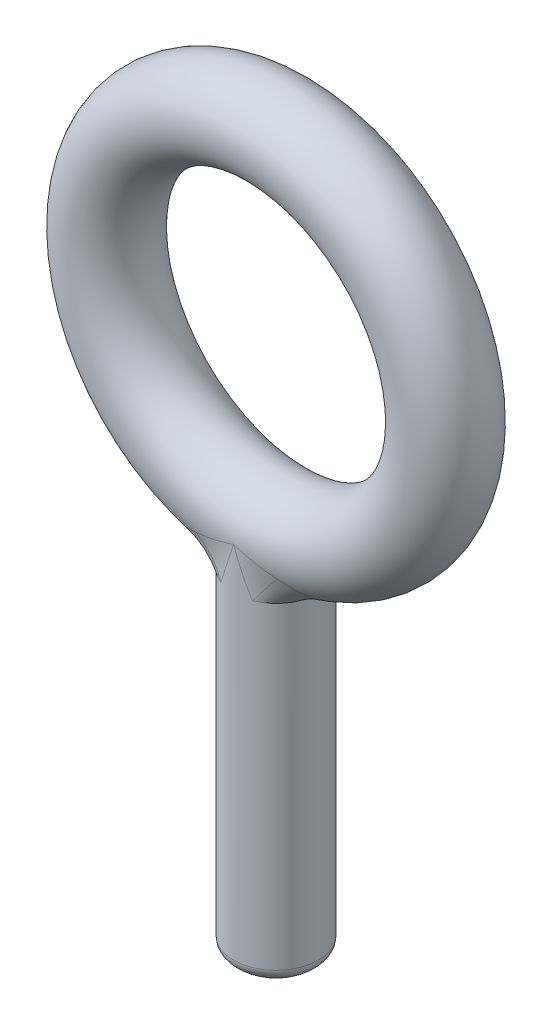
SolidWorks part; units mm, degrees
ref_plane "Front Plane" through (0, 0, 0) normal (0, 0, 1) x (1, 0, 0)
ref_plane "Top Plane" through (0, 0, 0) normal (0, 1, 0) x (1, 0, 0)
ref_plane "Right Plane" through (0, 0, 0) normal (1, 0, 0) x (0, 0, -1)
sketch "Sketch1" plane through (0, 0, 0) normal (0, 0, 1) x (1, 0, 0)
  line L0 (0, -15.875) -> (0, -41.275) construction
  line L1 (-3.175, -41.275) -> (3.175, -41.275) construction
  line L3 (0, -15.875) -> (0, -9.525) construction
  circle A0 centre (0, 0) radius 15.875 construction
  circle A1 centre (0, 12.7) radius 3.175 construction
  circle A2 centre (0, 0) radius 9.525 construction
  point P7 (0, -15.875)
  point P9 (0, -15.875)
  point P10 (0, 15.875)
  point P11 (0, 9.525)
  point P14 (0, -41.275)
  point P19 (0, -12.7)
  dimension "A" = 6.35
  dimension "Eye Dia." = 19.05
  dimension "Overall Lg." = 57.15
  dimension "Shank Lg." = 25.4
  dimension "OD" = 31.75
  dimension "Shank OD" = 6.35
sketch "Sketch2" plane through (0, 0, 0) normal (0, 1, 0) x (1, 0, 0)
  circle A0 centre (0, 0) radius 3.175
extrude "Boss-Extrude1" add sketch "Sketch2" against normal up to vertex (41.275 mm away) from vertex up to point (0, -41.275, 0) starting at point (0, -15.875, 0)
sketch "Sketch3" plane through (0, 0, 0) normal (1, 0, 0) x (0, 0, -1)
  circle A0 centre (0, 12.7) radius 3.175
ref_axis "Axis1" through (0, 0, -34.925) along (0, 0, 1)
revolve "Revolve1" add sketch "Sketch3" angle 360 about axis through (0, 0, -34.925) along (0, 0, 1)
sketch "Sketch4" plane through (0, -15.875, 0) normal (0, 1, 0) x (1, 0, 0)
  circle A1 centre (0, 0) radius 3.175
  circle A2 centre (0, 0) radius 3.175
  dimension "D1" = 0
extrude "Boss-Extrude2" [suppressed] add sketch "Sketch4" along normal up to vertex (9.525 mm away) up to point (0, -15.875, 0)
sketch "Sketch5" plane through (0, 0, 0) normal (0, 0, 1) x (1, 0, 0)
  line L0 (0, -15.875) -> (0, -12.7)
  line L1 (-3.175, -15.875) -> (0, -15.875)
  line L2 (-3.175, -12.7) -> (0, -12.7)
  line L3 (-3.175, -15.875) -> (-3.175, -12.7)
  line L4 (0, -15.875) -> (0, -9.525) construction
  circle A0 centre (0, -12.7) radius 3.175 construction
revolve "Revolve2" add sketch "Sketch5" angle 360 about L0
fillet "Fillet1" radius 6.35 2 edges at (3.1719, -15.5517, -0.14) (-3.1719, -15.5517, 0.14)
combine bodies "Combine1" operation type add bodies to combine 109 102
sketch "Sketch6" plane through (0, 0, 0) normal (0, 0, 1) x (1, 0, 0)
  line L0 (0, -42.8625) -> (-3.175, -42.8625)
  line L1 (-3.175, -42.8625) -> (-3.175, -39.6875)
  line L2 (0, -41.275) -> (0, -42.8625)
  line L4 (0, -15.875) -> (0, -41.275) construction
  line L5 (-3.175, -41.275) -> (3.175, -41.275) construction
  line L6 (0, -41.275) -> (-3.175, -41.275) construction
  line L7 (0, -38.1) -> (0, -41.275) construction
  ellipse E0 centre (0, -39.6875) end of major axis (3.175, -39.6875) minor radius 1.5875 (-3.175, -39.6875) -> (0, -41.275) ccw
revolve "Cut-Revolve1" cut sketch "Sketch6" angle 360 about L2
equation "\"D1@Fillet1\" = \"A@Sketch1\""
